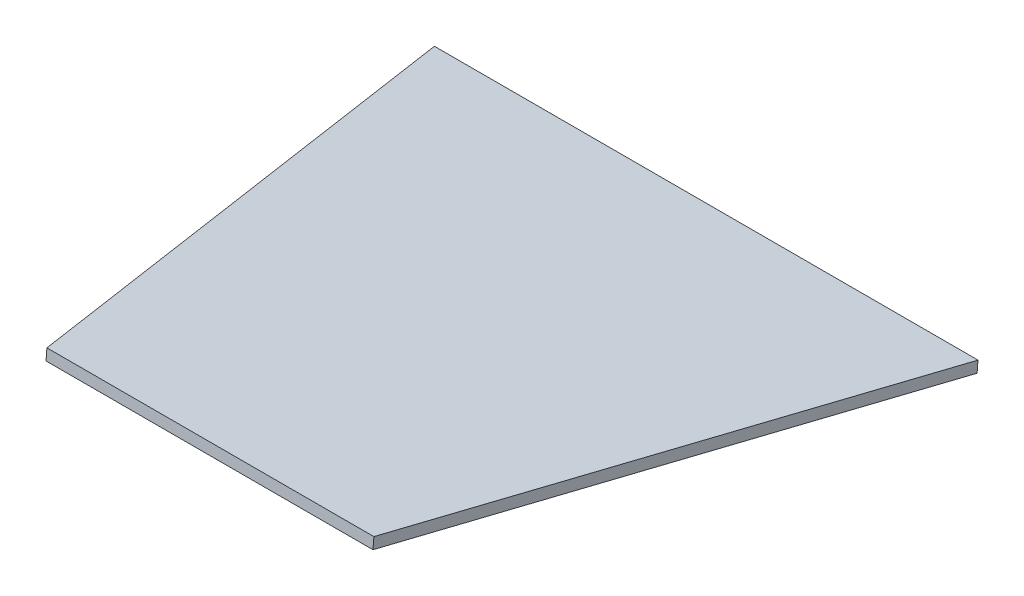
SolidWorks part; units mm, degrees
ref_plane "Front Plane" through (0, 0, 0) normal (0, 0, 1) x (1, 0, 0)
ref_plane "Top Plane" through (0, 0, 0) normal (0, 1, 0) x (1, 0, 0)
ref_plane "Right Plane" through (0, 0, 0) normal (1, 0, 0) x (0, 0, -1)
ref_plane "Plane1" through (-0.0003, -3154.5552, 260.2302) normal (0, -0.9966, 0.0822) x (-1, 0, 0)
sketch "Sketch1" plane through (-0.0003, -3154.5552, 260.2302) normal (0, -0.9966, 0.0822) x (-1, 0, 0)
  line L0 (927.9324, -1893.2884) -> (1306.8393, -1893.2884)
  line L1 (1306.8393, -1893.2884) -> (1432.3521, -1316.7398)
  line L2 (1432.3521, -1316.7398) -> (802.4196, -1316.7398)
  line L3 (802.4196, -1316.7398) -> (927.9324, -1893.2884)
  line L4 (802.4183, -1316.7398) -> (1432.3534, -1316.7398) construction
  line L5 (928.076, -1893.948) -> (801.0629, -1310.5075) construction
  line L6 (1433.7088, -1310.5075) -> (1306.6957, -1893.948) construction
  line L7 (1306.8419, -1893.2884) -> (927.9298, -1893.2884) construction
extrude "Boss-Extrude1" add sketch "Sketch1" along normal blind 12.7
